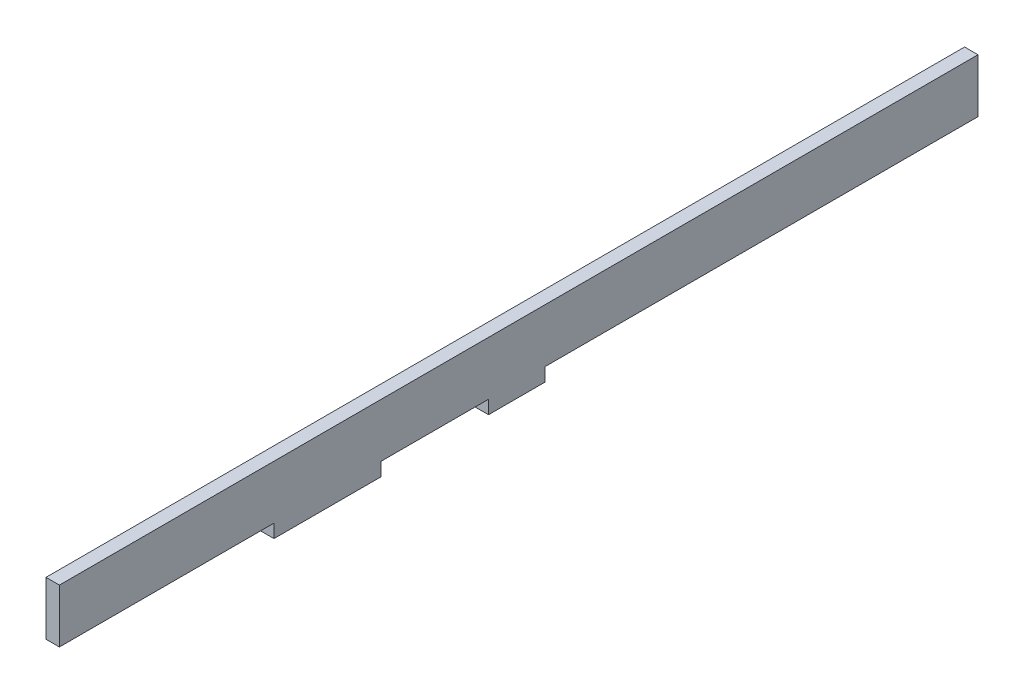
SolidWorks part; units mm, degrees
ref_plane "Front Plane" through (0, 0, 0) normal (0, 0, 1) x (1, 0, 0)
ref_plane "Top Plane" through (0, 0, 0) normal (0, 1, 0) x (1, 0, 0)
ref_plane "Right Plane" through (0, 0, 0) normal (1, 0, 0) x (0, 0, -1)
sketch "Sketch1" plane through (0, 0, 0) normal (1, 0, 0) x (0, 0, -1)
  line L7 (3.131, 0) -> (438.131, 0)
  line L8 (3.131, 0) -> (3.131, 31.75)
  line L9 (3.131, 31.75) -> (438.131, 31.75)
  line L10 (438.131, 0) -> (438.131, 31.75)
  dimension "D1" = 31.75
  dimension "D2" = 435
extrude "Boss-Extrude1" add sketch "Sketch1" along normal blind 6.35
sketch "Sketch2" plane through (0, 0, 0) normal (-1, 0, 0) x (0, 0, 1)
  line L1 (-3.131, 0) -> (-104.731, 0)
  line L2 (-3.131, 0) -> (-3.131, 6.35)
  line L3 (-3.131, 6.35) -> (-104.731, 6.35)
  line L4 (-104.731, 0) -> (-104.731, 6.35)
  dimension "D1" = 101.6
  dimension "D2" = 6.35
extrude "Cut-Extrude1" cut sketch "Sketch2" against normal up to next
sketch "Sketch3" plane through (0, 0, 0) normal (-1, 0, 0) x (0, 0, 1)
  line L0 (-104.731, 0) -> (-438.131, 0) construction
  line L1 (-155.531, 0) -> (-206.331, 0)
  line L2 (-155.531, 0) -> (-155.531, 6.35)
  line L3 (-155.531, 6.35) -> (-206.331, 6.35)
  line L4 (-206.331, 0) -> (-206.331, 6.35)
  line L5 (-104.731, 6.35) -> (-104.731, 0) construction
  line L6 (-233.131, 6.35) -> (-233.131, 0)
  line L7 (-233.131, 0) -> (-307.931, 0)
  line L9 (-233.131, 6.35) -> (-307.931, 6.35)
  line L11 (-438.131, 0) -> (-307.931, 0)
  line L12 (-438.131, 0) -> (-438.131, 6.35)
  line L13 (-438.131, 6.35) -> (-307.931, 6.35)
  dimension "D1" = 6.35
  dimension "D2" = 50.8
  dimension "D3" = 50.8
  dimension "D5" = 6.35
extrude "Cut-Extrude2" cut sketch "Sketch3" against normal up to next
